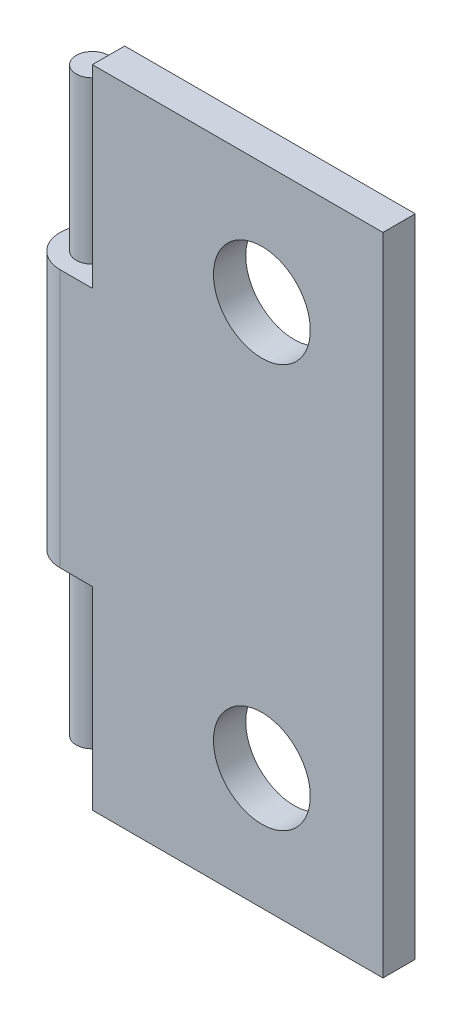
SolidWorks part; units mm, degrees
ref_plane "前视基准面" through (0, 0, 0) normal (0, 0, 1) x (1, 0, 0)
ref_plane "上视基准面" through (0, 0, 0) normal (0, 1, 0) x (1, 0, 0)
ref_plane "右视基准面" through (0, 0, 0) normal (1, 0, 0) x (0, 0, -1)
other "Configuration Table"
sketch "草图1" plane through (0, 0, 0) normal (0, 1, 0) x (1, 0, 0)
  line L1 (-10, -1) -> (10, -1)
  line L2 (-10, -1) -> (-10, 1)
  line L3 (-10, 1) -> (10, 1)
  line L4 (10, -1) -> (10, 1)
  line L5 (-10, -1) -> (10, 1) construction
  line L6 (-10, 1) -> (10, -1) construction
  circle A0 centre (-10, 1) radius 2
  circle A1 centre (-10, 1) radius 1
  point P0 (0, 0)
extrude "凸台-拉伸1" add sketch "草图1" along normal blind 40 contours A0 L1 L4 L3 | A1 L2 A0 L3 | L3 A1 L2 | L2 A1 L3 | A1 L3 A0 L2 region at (0.78, 0, 0.0129) region at (-11.3742, 0, -2.3742) region at (-9.0097, 0, -0.0097) region at (-10.1415, 0, -1.1415) region at (-9.5756, 0, -0.5756)
sketch "草图2" plane through (0, 0, -1) normal (0, 0, -1) x (-1, 0, 0)
  line L0 (12, 0) -> (12, 40) construction
  line L1 (8, 0) -> (12, 0)
  line L2 (8, 0) -> (8, 12)
  line L3 (8, 12) -> (12, 12)
  line L4 (12, 0) -> (12, 12)
  line L6 (8, 40) -> (12, 40)
  line L7 (8, 40) -> (8, 28)
  line L8 (8, 28) -> (12, 28)
  line L9 (12, 40) -> (12, 28)
extrude "切除-拉伸1" cut sketch "草图2" against normal blind 40 and the other way blind 40 contours L2 L1 L4 L3 | L7 L6 L9 L8
sketch "草图3" plane through (0, 12, 0) normal (0, -1, 0) x (-1, 0, 0)
  line L0 (8, 1) -> (10, 1)
  circle A0 centre (10, 1) radius 1
extrude "凸台-拉伸2" add sketch "草图3" along normal blind 10 contours A0 region at (-10, 12, -0.0283)
sketch "草图4" plane through (0, 28, 0) normal (0, 1, 0) x (1, 0, 0)
  line L0 (-10, 3) -> (-10, 1)
  arc A0 (-8, 1) -> (-10, -1) centre (-10, 1) ccw construction
  circle A1 centre (-10, 1) radius 1
extrude "凸台-拉伸3" add sketch "草图4" along normal blind 10 contours A1 region at (-10.6871, 28, -0.3129)
sketch "草图5" plane through (0, 0, -1) normal (0, 0, -1) x (-1, 0, 0)
  line L0 (-10, 40) -> (-10, 0) construction
  line L1 (-10, 40) -> (-2.5, 40)
  line L2 (-10, 40) -> (-10, 32.5)
  line L3 (-10, 32.5) -> (-2.5, 32.5)
  line L4 (-2.5, 40) -> (-2.5, 32.5)
  line L5 (-10, 0) -> (-2.5, 0)
  line L6 (-10, 0) -> (-10, 7.5)
  line L7 (-10, 7.5) -> (-2.5, 7.5)
  line L8 (-2.5, 0) -> (-2.5, 7.5)
  circle A0 centre (-2.5, 32.5) radius 3
  circle A1 centre (-2.5, 7.5) radius 3
extrude "切除-拉伸2" cut sketch "草图5" against normal blind 10 contours L4 A0 L3 | L3 A0 L4 | L7 A1 L8 | L8 A1 L7 region at (2.0756, 32.0756, -1) region at (3.7732, 33.7732, -1) region at (3.7732, 6.2268, -1) region at (2.0756, 7.9244, -1)
